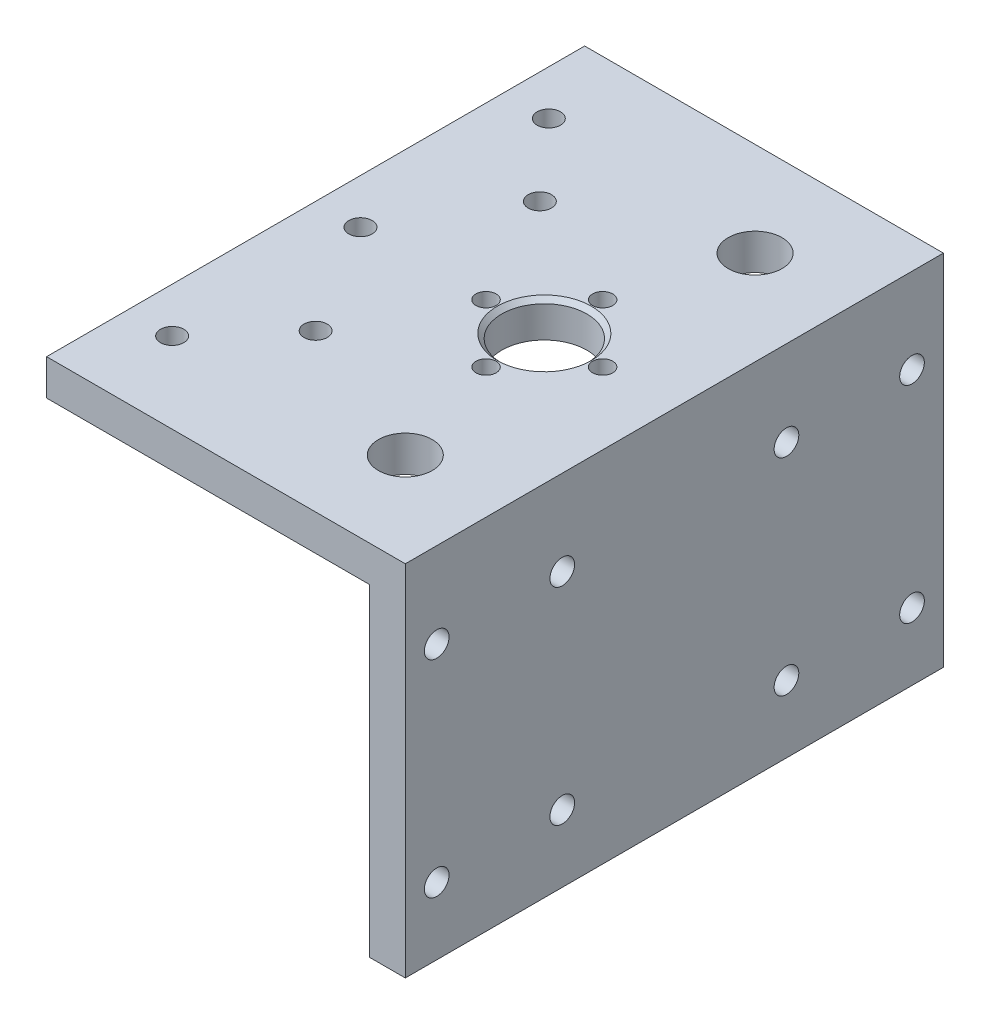
SolidWorks part; units mm, degrees
material "Lega 1060"
ref_plane "Piano frontale" through (0, 0, 0) normal (0, 0, 1) x (1, 0, 0)
ref_plane "Piano superiore" through (0, 0, 0) normal (0, 1, 0) x (1, 0, 0)
ref_plane "Piano destro" through (0, 0, 0) normal (1, 0, 0) x (0, 0, -1)
sketch "Schizzo1" plane through (0, 0, 0) normal (0, 0, 1) x (1, 0, 0)
  line L0 (0, 0) -> (-80, 0)
  line L1 (-80, 0) -> (-80, -8)
  line L2 (-80, -8) -> (-8, -8)
  line L3 (-8, -8) -> (-8, -80)
  line L4 (-8, -80) -> (0, -80)
  line L5 (0, -80) -> (0, 0)
  dimension "D1" = 80
  dimension "D2" = 80
  dimension "D3" = 8
  dimension "D4" = 8
extrude "Estrusione-Estrusione1" add sketch "Schizzo1" along normal blind 120
sketch "Schizzo12" plane through (0, 0, 0) normal (1, 0, 0) x (0, 0, -1)
  line L0 (0, -8) -> (-120, -8) construction
  line L1 (-21, 0) -> (-21, 18.8536) construction
  line L5 (0, -80) -> (0, 0) construction
  line L6 (-120, -80) -> (-120, 0) construction
  line L7 (-120, 0) -> (0, 0) construction
  line L8 (-113, -19) -> (10.4492, -19) construction
  line L9 (-113, -65) -> (16.1501, -65) construction
  line L10 (-99, -47.4454) -> (-99, 40.839) construction
  circle A0 centre (-113, -19) radius 2.75
  circle A1 centre (-85, -19) radius 2.75
  circle A6 centre (-35, -19) radius 2.75
  circle A7 centre (-7, -19) radius 2.75
  circle A10 centre (-85, -65) radius 2.75
  circle A11 centre (-113, -65) radius 2.75
  circle A12 centre (-7, -65) radius 2.75
  circle A13 centre (-35, -65) radius 2.75
  dimension "D1" = 5.5
  dimension "D5" = 28
  dimension "D6" = 28
  dimension "D7" = 28
  dimension "D8" = 28
  dimension "D2" = 8
  dimension "D3" = 11
  dimension "D4" = 57
  dimension "D9" = 21
  dimension "D10" = 21
sketch "Schizzo6" plane through (0, 0, 0) normal (0, 1, 0) x (1, 0, 0)
  line L0 (-21, -0.5808) -> (-21, -110.5835) construction
  line L2 (0, 0) -> (-80, 0) construction
  line L3 (-32.5218, -60) -> (-8.0464, -60) construction
  line L6 (0, -120) -> (-80, -120) construction
  circle A0 centre (-21, -21) radius 6
  circle A1 centre (-21, -99) radius 6
  dimension "D2" = 12
  dimension "D1" = 13
  dimension "D3" = 21
extrude "Taglio-Estrusione2" cut sketch "Schizzo6" against normal up to next
sketch "Schizzo7" plane through (0, 0, 0) normal (0, 1, 0) x (1, 0, 0)
  line L0 (-53.636, -60) -> (3.6289, -60) construction
  line L1 (0, -120) -> (-80, -120) construction
  line L2 (0, 0) -> (-80, 0) construction
  line L3 (-21, -21) -> (-21, -99) construction
  circle A0 centre (-29, -60) radius 9.5
  dimension "D1" = 19
  dimension "D2" = 8
extrude "Taglio-Estrusione3" cut sketch "Schizzo7" against normal up to next
hole_wizard "Foro per Vite M4-2" positions "Schizzo9" profile "Schizzo8" hole size "M4" standard "ISO" end condition through all
sketch "Schizzo9" plane through (0, 0, 0) normal (0, 1, 0) x (1, 0, 0)
  line L0 (-18.4657, -60) -> (-16, -60) construction
  line L2 (-29, -57.7684) -> (-29, -66.5063) construction
  circle A2 centre (-29, -60) radius 9.5 construction
  point P0 (-29, -47)
  point P2 (-42, -60)
  point P4 (-29, -73)
  point P8 (-16, -60)
  point P20 (-29, -60)
  dimension "D1" = 26
  dimension "D2" = 13
  dimension "D3" = 13
sketch "Schizzo8" plane through (-29, 0, 47) normal (1, 0, 0) x (0, 0, 1)
  line L0 (0, 0) -> (0, 80)
  line L1 (0, 80) -> (2.25, 80)
  line L2 (2.25, 80) -> (2.25, 0)
  line L5 (2.25, 0) -> (0, 0)
  line L11 (0, -6.35) -> (0, 107.95) construction
  dimension "Thru Hole Dia." = 4.5
  dimension "Thru Hole Depth" = 80
extrude "Taglio-Estrusione4" cut sketch "Schizzo12" against normal blind 10
sketch "Schizzo14" plane through (0, 0, 0) normal (0, 1, 0) x (1, 0, 0)
  line L0 (-70, 0) -> (-70, -120) construction
  line L1 (0, 0) -> (-80, 0) construction
  line L2 (0, -120) -> (-80, -120) construction
  line L3 (-80, -120) -> (-80, 0) construction
  line L4 (-55, 0) -> (-55, -120) construction
  line L5 (-21, -99) -> (-80, -99) construction
  line L6 (-80, -60) -> (0, -60) construction
  line L7 (0, -120) -> (0, 0) construction
  line L8 (-21, -21) -> (-80, -21) construction
  circle A0 centre (-70, -18) radius 2.6
  circle A1 centre (-70, -60) radius 2.6
  circle A2 centre (-70, -102) radius 2.6
  circle A3 centre (-55, -35) radius 2.6
  circle A4 centre (-55, -85) radius 2.6
  dimension "D3" = 5.2
  dimension "D4" = 5.2
  dimension "D5" = 5.2
  dimension "D6" = 5.2
  dimension "D7" = 5.2
  dimension "D1" = 10
  dimension "D2" = 25
  dimension "D8" = 35
  dimension "D9" = 35
  dimension "D10" = 25
  dimension "D11" = 42
  dimension "D12" = 15
extrude "Taglio-Estrusione5" cut sketch "Schizzo14" against normal blind 10
chamfer "Smusso2" distance 1 angle 45 1 edges at (-38.5, 0, 60)
